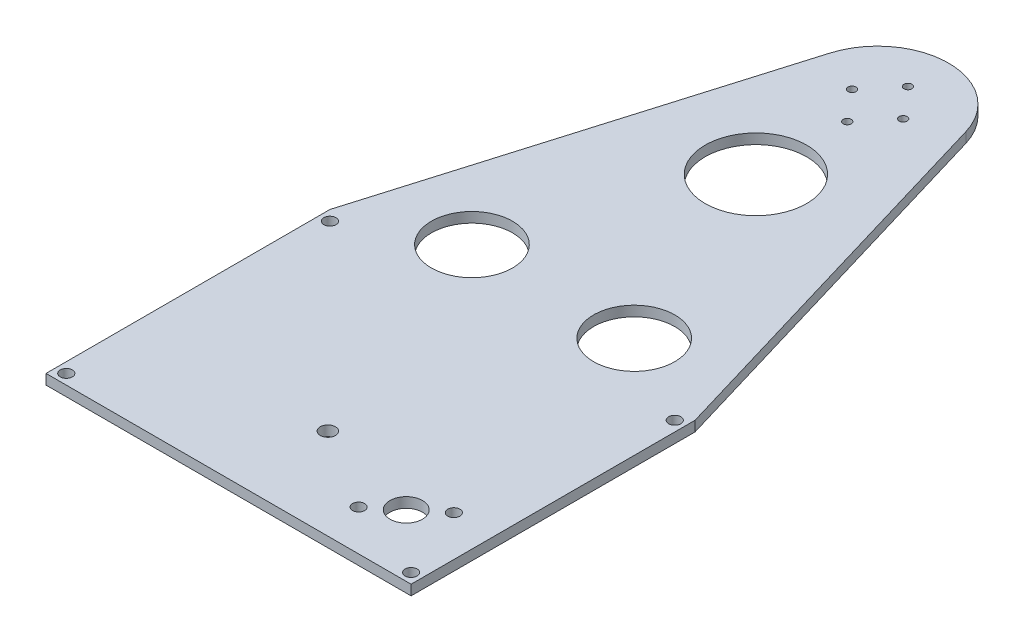
SolidWorks part; units mm, degrees
material "PLA/ABS"
ref_plane "Front Plane" through (0, 0, 0) normal (0, 0, 1) x (1, 0, 0)
ref_plane "Top Plane" through (0, 0, 0) normal (0, 1, 0) x (1, 0, 0)
ref_plane "Right Plane" through (0, 0, 0) normal (1, 0, 0) x (0, 0, -1)
other "Bounding Box"
ref_plane "Default Plane" through (-8.9266, -12.7485, 0) normal (-0.1736, 0.9848, 0) x (0.9848, 0.1736, 0)
sketch "Sketch1" plane through (0, 0, 0) normal (0, 1, 0) x (1, 0, 0)
  line L0 (0, 0) -> (0, -133.35) construction
  line L1 (0, -133.35) -> (-6.35, -133.35) construction
  line L2 (-63.5, -133.35) -> (-57.15, -133.35) construction
  line L3 (-57.15, -143.3195) -> (-6.35, -143.3195)
  line L4 (-57.15, -143.3195) -> (-57.15, -123.3805)
  line L5 (-57.15, -123.3805) -> (-6.35, -123.3805)
  line L6 (-6.35, -143.3195) -> (-6.35, -123.3805)
  line L7 (-57.15, -143.3195) -> (-6.35, -123.3805) construction
  line L8 (-57.15, -123.3805) -> (-6.35, -143.3195) construction
  line L9 (-88.9, -167.386) -> (-63.5, -167.386)
  line L10 (-88.9, -167.386) -> (-88.9, -99.314)
  line L11 (-88.9, -99.314) -> (-63.5, -99.314)
  line L12 (-63.5, -167.386) -> (-63.5, -99.314)
  line L13 (-88.9, -167.386) -> (-63.5, -99.314) construction
  line L14 (-88.9, -99.314) -> (-63.5, -167.386) construction
  line L15 (57.15, -123.3805) -> (6.35, -123.3805)
  line L16 (-50.8, -196.85) -> (6.35, -196.85)
  line L17 (-50.8, -196.85) -> (-50.8, -180.34)
  line L18 (-50.8, -180.34) -> (6.35, -180.34)
  line L19 (6.35, -196.85) -> (6.35, -180.34)
  line L20 (-50.8, -196.85) -> (6.35, -180.34) construction
  line L21 (-50.8, -180.34) -> (6.35, -196.85) construction
  line L22 (6.35, -143.3195) -> (6.35, -123.3805)
  line L23 (57.15, -143.3195) -> (6.35, -143.3195)
  line L24 (57.15, -143.3195) -> (57.15, -123.3805)
  line L25 (88.9, -99.314) -> (63.5, -99.314)
  line L26 (63.5, -167.386) -> (63.5, -99.314)
  line L27 (88.9, -167.386) -> (63.5, -167.386)
  line L28 (88.9, -167.386) -> (88.9, -99.314)
  line L30 (50.8, -196.85) -> (7.62, -196.85)
  line L31 (50.8, -196.85) -> (50.8, -176.7078)
  line L32 (50.8, -176.7078) -> (7.62, -176.7078)
  line L33 (7.62, -196.85) -> (7.62, -176.7078)
  line L34 (50.8, -196.85) -> (7.62, -176.7078) construction
  line L35 (50.8, -176.7078) -> (7.62, -196.85) construction
  line L36 (-57.15, -203.2) -> (57.15, -203.2)
  line L37 (-57.15, -203.2) -> (-57.15, -114.3)
  line L38 (-57.15, -114.3) -> (57.15, -114.3)
  line L39 (57.15, -203.2) -> (57.15, -114.3)
  line L40 (-57.15, -203.2) -> (57.15, -114.3) construction
  line L41 (-57.15, -114.3) -> (57.15, -203.2) construction
  circle A0 centre (0, 0) radius 38.1
  circle A1 centre (0, 0) radius 13.843
  point P3 (-22.225, -188.595)
  point P6 (-31.75, -133.35)
  point P12 (-76.2, -133.35)
  point P22 (0, -114.3)
  point P23 (0, -158.75)
  point P36 (0, -38.1)
  point P38 (29.21, -186.7789)
  dimension "D1" = 76.2
  dimension "D19" = 27.686
  dimension "D2" = 50.8
  dimension "D3" = 19.939
  dimension "D4" = 68.072
  dimension "D5" = 25.4
  dimension "D6" = 57.15
  dimension "D7" = 16.51
  dimension "D8" = 43.18
  dimension "D9" = 20.1422
  dimension "D10" = 76.2
  dimension "D11" = 114.3
  dimension "D12" = 19.05
  dimension "D13" = 6.35
  dimension "D14" = 6.35
  dimension "D15" = 6.35
  dimension "D16" = 6.35
  dimension "D17" = 88.9
  dimension "D18" = 6.35
sketch "Sketch2" plane through (0, 0, 0) normal (1, 0, 0) x (0, 0, -1)
  line L1 (-203.2, 12.7) -> (-114.3, 12.7)
  line L2 (-203.2, 12.7) -> (-203.2, -12.7)
  line L3 (-203.2, -12.7) -> (-114.3, -12.7)
  line L4 (-114.3, 12.7) -> (-114.3, -12.7)
  line L5 (-203.2, 12.7) -> (-114.3, -12.7) construction
  line L6 (-203.2, -12.7) -> (-114.3, 12.7) construction
  line L7 (-203.2, 12.7) -> (12.7, 12.7)
  line L8 (-203.2, 12.7) -> (-203.2, 15.875)
  line L9 (-203.2, 15.875) -> (12.7, 15.875)
  line L10 (12.7, 12.7) -> (12.7, 15.875)
  line L11 (-203.2, 12.7) -> (12.7, 15.875) construction
  line L12 (-203.2, 15.875) -> (12.7, 12.7) construction
  line L13 (-203.2, -12.7) -> (-114.3, -12.7)
  line L14 (-203.2, -12.7) -> (-203.2, -15.875)
  line L15 (-203.2, -15.875) -> (-114.3, -15.875)
  line L16 (-114.3, -12.7) -> (-114.3, -15.875)
  line L17 (-203.2, -12.7) -> (-114.3, -15.875) construction
  line L18 (-203.2, -15.875) -> (-114.3, -12.7) construction
  circle A0 centre (-133.35, 0) radius 34.036
  point P4 (-167.386, 0)
  point P5 (-158.75, 0)
  point P15 (-95.25, 14.2875)
  point P19 (-158.75, -14.2875)
  dimension "D1" = 25.4
  dimension "D2" = 3.175
  dimension "D3" = 12.7
sketch "Sketch3" plane through (0, 0, 0) normal (0, 1, 0) x (1, 0, 0)
  line L1 (-57.15, -203.2) -> (57.15, -203.2)
  line L2 (-57.15, -203.2) -> (-57.15, -114.3)
  line L3 (-57.15, -114.3) -> (57.15, -114.3)
  line L4 (57.15, -203.2) -> (57.15, -114.3)
  line L5 (-57.15, -203.2) -> (57.15, -114.3) construction
  line L6 (-57.15, -114.3) -> (57.15, -203.2) construction
  line L7 (-50.8, -120.65) -> (50.8, -120.65)
  line L8 (-50.8, -120.65) -> (-50.8, -196.85)
  line L9 (-50.8, -196.85) -> (50.8, -196.85)
  line L10 (50.8, -120.65) -> (50.8, -196.85)
  line L11 (-50.8, -120.65) -> (50.8, -196.85) construction
  line L12 (-50.8, -196.85) -> (50.8, -120.65) construction
  point P0 (0, -158.75)
  point P7 (0, -158.75)
extrude "Boss-Extrude1" add sketch "Sketch3" along normal up to vertex (12.7 mm away) and the other way up to vertex (12.7 mm away) up to point (0, 12.7, 203.2) other way up to point (0, -12.7, 203.2)
sketch "Sketch4" plane through (0, -12.7, 0) normal (0, -1, 0) x (1, 0, 0)
  line L1 (-57.15, 203.2) -> (57.15, 203.2)
  line L2 (-57.15, 203.2) -> (-57.15, 114.3)
  line L3 (-57.15, 114.3) -> (57.15, 114.3)
  line L4 (57.15, 203.2) -> (57.15, 114.3)
  line L5 (-57.15, 203.2) -> (57.15, 114.3) construction
  line L6 (-57.15, 114.3) -> (57.15, 203.2) construction
  point P0 (0, 158.75)
extrude "Boss-Extrude2" add sketch "Sketch4" along normal up to vertex (3.175 mm away) up to point (0, -15.875, 203.2)
sketch "Sketch5" plane through (0, 12.7, 0) normal (0, 1, 0) x (1, 0, 0)
  line L0 (-21.3043, 6.3306) -> (-57.15, -114.3)
  line L1 (-57.15, -114.3) -> (-57.15, -203.2)
  line L2 (-57.15, -203.2) -> (57.15, -203.2)
  line L3 (57.15, -203.2) -> (57.15, -114.3)
  line L4 (57.15, -114.3) -> (21.3043, 6.3306)
  arc A0 (-21.3043, 6.3306) -> (21.3043, 6.3306) centre (0, 0) cw
  dimension "D1" = 22.225
extrude "Boss-Extrude3" add sketch "Sketch5" along normal up to vertex (3.175 mm away) separate body up to point (0, 15.875, 203.2)
sketch "Sketch7" plane through (0, -12.7, 0) normal (0, 1, 0) x (1, 0, 0)
  line L0 (-6.35, -143.3195) -> (-6.35, -123.3805) construction
  line L1 (-50.8, -120.65) -> (-6.35, -120.65)
  line L2 (-50.8, -120.65) -> (-50.8, -146.05)
  line L3 (-50.8, -146.05) -> (-6.35, -146.05)
  line L4 (-6.35, -120.65) -> (-6.35, -146.05)
  line L5 (-50.8, -120.65) -> (-6.35, -146.05) construction
  line L6 (-50.8, -146.05) -> (-6.35, -120.65) construction
  line L7 (50.8, -120.65) -> (6.35, -120.65)
  line L8 (50.8, -120.65) -> (50.8, -146.05)
  line L9 (50.8, -146.05) -> (6.35, -146.05)
  line L10 (6.35, -120.65) -> (6.35, -146.05)
  line L11 (50.8, -120.65) -> (6.35, -146.05) construction
  line L12 (50.8, -146.05) -> (6.35, -120.65) construction
  line L13 (6.35, -143.3195) -> (6.35, -123.3805) construction
  line L14 (0, -133.35) -> (-6.35, -133.35) construction
  point P4 (-28.575, -133.35)
  point P10 (28.575, -133.35)
extrude "Boss-Extrude4" add sketch "Sketch7" along normal blind 6.35
sketch "Sketch6" plane through (-57.15, 0, 0) normal (-1, 0, 0) x (0, 0, 1)
  circle A0 centre (133.35, 0) radius 9.9695
extrude "Cut-Extrude1" cut sketch "Sketch6" against normal through all
ref_plane "Plane1" through (0, 0, 0) normal (1, 0, 0) x (0, 0, -1)
sketch "Sketch13" plane through (0, -12.7, 0) normal (0, 1, 0) x (1, 0, 0)
  line L0 (-50.8, -146.05) -> (-6.35, -146.05) construction
  line L1 (-6.35, -120.65) -> (-35.56, -120.65)
  line L2 (-6.35, -120.65) -> (-6.35, -146.05)
  line L3 (-6.35, -146.05) -> (-35.56, -146.05)
  line L4 (-35.56, -120.65) -> (-35.56, -146.05)
  line L5 (-6.35, -120.65) -> (-35.56, -146.05) construction
  line L6 (-6.35, -146.05) -> (-35.56, -120.65) construction
  line L7 (-50.8, -120.65) -> (-50.8, -125.6644) construction
  line L9 (0, -17.4625) -> (0, 17.4625) construction
  line L10 (35.56, -120.65) -> (35.56, -146.05)
  line L11 (6.35, -146.05) -> (35.56, -146.05)
  line L12 (6.35, -120.65) -> (6.35, -146.05)
  line L13 (6.35, -120.65) -> (35.56, -120.65)
  point P4 (-20.955, -133.35)
  dimension "D1" = 15.24
extrude "Boss-Extrude5" add sketch "Sketch13" along normal blind 4.064
sketch "Sketch14" plane through (0, 0, 146.05) normal (0, 0, 1) x (1, 0, 0)
  line L0 (-35.56, -8.0762) -> (-35.56, -11.2291) construction
  line L1 (-30.48, -9.144) -> (-24.13, -9.144)
  line L2 (-30.48, -9.144) -> (-30.48, -11.684)
  line L3 (-30.48, -11.684) -> (-24.13, -11.684)
  line L4 (-24.13, -9.144) -> (-24.13, -11.684)
  line L5 (-30.48, -9.144) -> (-24.13, -11.684) construction
  line L6 (-30.48, -11.684) -> (-24.13, -9.144) construction
  line L7 (-35.56, -8.636) -> (-35.56, -9.9695) construction
  line L8 (-6.35, -6.35) -> (-50.8, -6.35) construction
  line L9 (-30.48, -5.08) -> (-24.13, -5.08)
  line L10 (-30.48, -5.08) -> (-30.48, -2.54)
  line L11 (-30.48, -2.54) -> (-24.13, -2.54)
  line L12 (-24.13, -5.08) -> (-24.13, -2.54)
  line L13 (-30.48, -5.08) -> (-24.13, -2.54) construction
  line L14 (-30.48, -2.54) -> (-24.13, -5.08) construction
  line L15 (-50.8, -12.7) -> (-6.35, -12.7) construction
  line L16 (0, -17.4625) -> (0, 17.4625) construction
  line L17 (30.48, -11.684) -> (24.13, -11.684)
  line L18 (24.13, -9.144) -> (24.13, -11.684)
  line L19 (30.48, -9.144) -> (24.13, -9.144)
  line L20 (30.48, -9.144) -> (30.48, -11.684)
  line L21 (30.48, -2.54) -> (24.13, -2.54)
  line L22 (24.13, -5.08) -> (24.13, -2.54)
  line L23 (30.48, -5.08) -> (24.13, -5.08)
  line L24 (30.48, -5.08) -> (30.48, -2.54)
  point P4 (-27.305, -10.414)
  point P13 (-27.305, -3.81)
  dimension "D1" = 2.54
  dimension "D2" = 6.35
  dimension "D3" = 5.08
  dimension "D4" = 1.27
  dimension "D5" = 1.016
extrude "Cut-Extrude2" cut sketch "Sketch14" against normal up to surface (31.75 mm away) up to face at (0, -1.5875, 114.3)
sketch "Sketch18" plane through (0, 0, 120.65) normal (0, 0, 1) x (1, 0, 0)
  line L0 (50.8, 12.7) -> (-50.8, 12.7) construction
  line L1 (-48.26, 12.7) -> (-38.1, 12.7)
  line L2 (-48.26, 12.7) -> (-48.26, 7.62)
  line L3 (-48.26, 7.62) -> (-38.1, 7.62)
  line L4 (-38.1, 12.7) -> (-38.1, 7.62)
  line L5 (-48.26, 12.7) -> (-38.1, 7.62) construction
  line L6 (-48.26, 7.62) -> (-38.1, 12.7) construction
  line L7 (-50.8, 12.7) -> (-50.8, -6.35) construction
  point P4 (-43.18, 10.16)
  dimension "D1" = 10.16
  dimension "D2" = 2.54
  dimension "D3" = 5.08
extrude "Cut-Extrude3" cut sketch "Sketch18" against normal up to surface (6.35 mm away) up to face at (-27.305, -3.81, 114.3)
sketch "Sketch19" plane through (0, 12.7, 0) normal (0, 1, 0) x (1, 0, 0)
  line L0 (-57.15, -114.3) -> (-57.15, -203.2) construction
  line L1 (-48.26, -114.3) -> (-57.15, -114.3) construction
  line L2 (-50.8, -120.65) -> (-50.8, -196.85) construction
  line L5 (57.15, -203.2) -> (57.15, -114.3) construction
  line L6 (57.15, -114.3) -> (-38.1, -114.3) construction
  line L7 (-57.15, -203.2) -> (57.15, -203.2) construction
  line L8 (-50.8, -196.85) -> (50.8, -196.85) construction
  circle A0 centre (-53.975, -117.475) radius 3.175 construction
  circle A1 centre (-53.975, -117.475) radius 0.635
  circle A2 centre (53.975, -117.475) radius 3.175 construction
  circle A3 centre (53.975, -117.475) radius 0.635
  circle A4 centre (-53.975, -200.025) radius 3.175 construction
  circle A5 centre (-53.975, -200.025) radius 0.635
  circle A6 centre (53.975, -200.025) radius 3.175 construction
  circle A7 centre (53.975, -200.025) radius 0.635
  dimension "D1" = 1.27
  dimension "D2" = 6.35
extrude "Cut-Extrude4" cut sketch "Sketch19" against normal blind 25.4
sketch "Sketch20" plane through (0, 15.875, 0) normal (0, 1, 0) x (1, 0, 0)
  circle A0 centre (-53.975, -117.475) radius 1.905
  circle A1 centre (-53.975, -200.025) radius 1.905
  circle A2 centre (53.975, -200.025) radius 1.905
  circle A3 centre (53.975, -117.475) radius 1.905
  dimension "D1" = 3.81
  dimension "D2" = 3.81
  dimension "D3" = 3.81
  dimension "D4" = 3.81
extrude "Cut-Extrude7" cut sketch "Sketch20" against normal up to surface (3.175 mm away) up to face at (0, 12.7, 101.0741)
sketch "Sketch23" plane through (0, 15.875, 0) normal (0, 1, 0) x (1, 0, 0)
  line L0 (-57.15, -203.2) -> (57.15, -203.2) construction
  line L1 (44.45, -177.1085) -> (28.015, -177.1085) construction
  line L2 (44.45, -177.1085) -> (44.45, -190.5) construction
  line L3 (44.45, -190.5) -> (28.015, -190.5) construction
  line L4 (28.015, -177.1085) -> (28.015, -190.5) construction
  line L5 (44.45, -177.1085) -> (28.015, -190.5) construction
  line L6 (44.45, -190.5) -> (28.015, -177.1085) construction
  line L7 (57.15, -203.2) -> (57.15, -114.3) construction
  circle A0 centre (36.2325, -183.8043) radius 5.08
  circle A1 centre (44.45, -177.1085) radius 1.905
  circle A2 centre (28.015, -190.5) radius 1.905
  circle A4 centre (2.615, -174.7273) radius 2.3812
  point P0 (36.2325, -183.8043)
  dimension "D1" = 10.16
  dimension "D2" = 3.81
  dimension "D3" = 10.6
  dimension "D4" = 12.7
  dimension "D7" = 4.7625
  dimension "D8" = 25.4
  dimension "D5" = 12.7
  dimension "D6" = 13.3915
extrude "Cut-Extrude8" cut sketch "Sketch23" against normal up to surface (3.175 mm away) up to face at (53.975, 12.7, 115.57)
sketch "Sketch24" plane through (0, 15.875, 0) normal (0, 1, 0) x (1, 0, 0)
  circle A0 centre (0, 0) radius 8 construction
  circle A1 centre (0, 0) radius 9.5 construction
  circle A2 centre (0, 9.5) radius 1.25
  circle A3 centre (0, -9.5) radius 1.25
  circle A4 centre (-8, 0) radius 1.25
  circle A5 centre (8, 0) radius 1.25
  dimension "D1" = 19
  dimension "D2" = 16
  dimension "D3" = 2.5
  dimension "D4" = 2.5
  dimension "D5" = 2.5
  dimension "D6" = 2.5
extrude "Cut-Extrude9" cut sketch "Sketch24" against normal up to surface (3.175 mm away) up to face at (2.615, 12.7, 172.346)
sketch "Sketch26" plane through (57.15, 0, 0) normal (1, 0, 0) x (0, 0, -1)
  line L0 (-203.2, 12.7) -> (-203.454, 12.7)
  line L1 (-203.454, 12.7) -> (-203.454, 15.875)
  line L2 (-203.454, 15.875) -> (-204.724, 15.875)
  line L3 (-204.724, 15.875) -> (-213.2314, -15.875)
  line L4 (-213.2314, -15.875) -> (-203.2, -15.875)
  line L6 (-203.2, -15.875) -> (-203.2, 12.7)
  line L7 (-265.8932, -34.036) -> (49734.1068, -34.036) construction
  line L8 (-203.2, 15.875) -> (12.7, 15.875) construction
  circle A0 centre (-133.35, 0) radius 34.036 construction
  dimension "D2" = 0.254
  dimension "D3" = 75
  dimension "D4" = 1.27
extrude "Boss-Extrude7" add sketch "Sketch26" against normal up to surface (114.3 mm away) up to face at (-57.15, 0, 143.3195)
sketch "Sketch27" plane through (0, -15.875, 0) normal (0, -1, 0) x (1, 0, 0)
  line L0 (57.15, 171.45) -> (95.25, 171.45)
  line L1 (57.15, 203.2) -> (57.15, 114.3) construction
  line L2 (95.25, 171.45) -> (95.25, 128.27)
  line L3 (95.25, 128.27) -> (100.33, 128.27)
  line L4 (100.33, 128.27) -> (100.33, 176.5362)
  line L5 (100.33, 176.5362) -> (57.15, 184.15)
  line L6 (57.15, 184.15) -> (57.15, 171.45)
  line L7 (57.15, 143.3195) -> (57.15, 123.3805) construction
  line L8 (0, 133.35) -> (-6.35, 133.35) construction
  line L9 (0, 0) -> (0, 227.7127) construction
  line L10 (-100.33, 176.5362) -> (-57.15, 184.15)
  line L11 (-100.33, 128.27) -> (-100.33, 176.5362)
  line L12 (-95.25, 128.27) -> (-100.33, 128.27)
  line L13 (-95.25, 171.45) -> (-95.25, 128.27)
  line L14 (-57.15, 171.45) -> (-95.25, 171.45)
  line L15 (-57.15, 184.15) -> (-57.15, 171.45)
  dimension "D1" = 38.1
  dimension "D2" = 5.08
  dimension "D3" = 5.08
  dimension "D4" = 38.1
  dimension "D5" = 10
  dimension "D6" = 12.7
extrude "Boss-Extrude8" add sketch "Sketch27" against normal up to surface (28.575 mm away) up to face at (0, 12.7, -10.75)
sketch "Sketch25" plane through (0, 15.875, 0) normal (0, 1, 0) x (1, 0, 0)
  line L0 (-25.4, -101.6) -> (0, -38.1) construction
  line L1 (0, -38.1) -> (25.4, -101.6) construction
  line L2 (25.4, -101.6) -> (-25.4, -101.6) construction
  line L3 (0, -101.6) -> (0, 0) construction
  line L4 (-57.15, -114.3) -> (57.15, -114.3) construction
  circle A0 centre (0, -38.1) radius 15.875
  circle A1 centre (-25.4, -101.6) radius 12.7
  circle A2 centre (25.4, -101.6) radius 12.7
  arc A3 (21.3043, 6.3306) -> (-21.3043, 6.3306) centre (0, 0) ccw construction
  dimension "D1" = 31.75
  dimension "D2" = 25.4
  dimension "D3" = 50.8
extrude "Cut-Extrude10" cut sketch "Sketch25" against normal through all
fillet "Fillet1" radius 9.525 6 edges at (95.25, -1.5875, 171.45) (-95.25, -1.5875, 171.45) (100.33, -1.5875, 176.5362) (-100.33, -1.5875, 176.5362) (57.15, -1.5875, 184.15) (-57.15, -1.5875, 184.15)
fillet "Fillet2" radius 5.08 2 edges at (57.15, -1.5875, 171.45) (-57.15, -1.5875, 171.45)
fillet "Fillet3" radius 9.525 4 edges at (-97.79, 12.7, 128.27) (-97.79, -15.875, 128.27) (97.79, -15.875, 128.27) (97.79, 12.7, 128.27)
delete or keep bodies "Body-Delete/Keep 1" type delete bodies bodies 121
delete or keep bodies "Body-Delete/Keep 2" [suppressed] type delete bodies bodies 118
